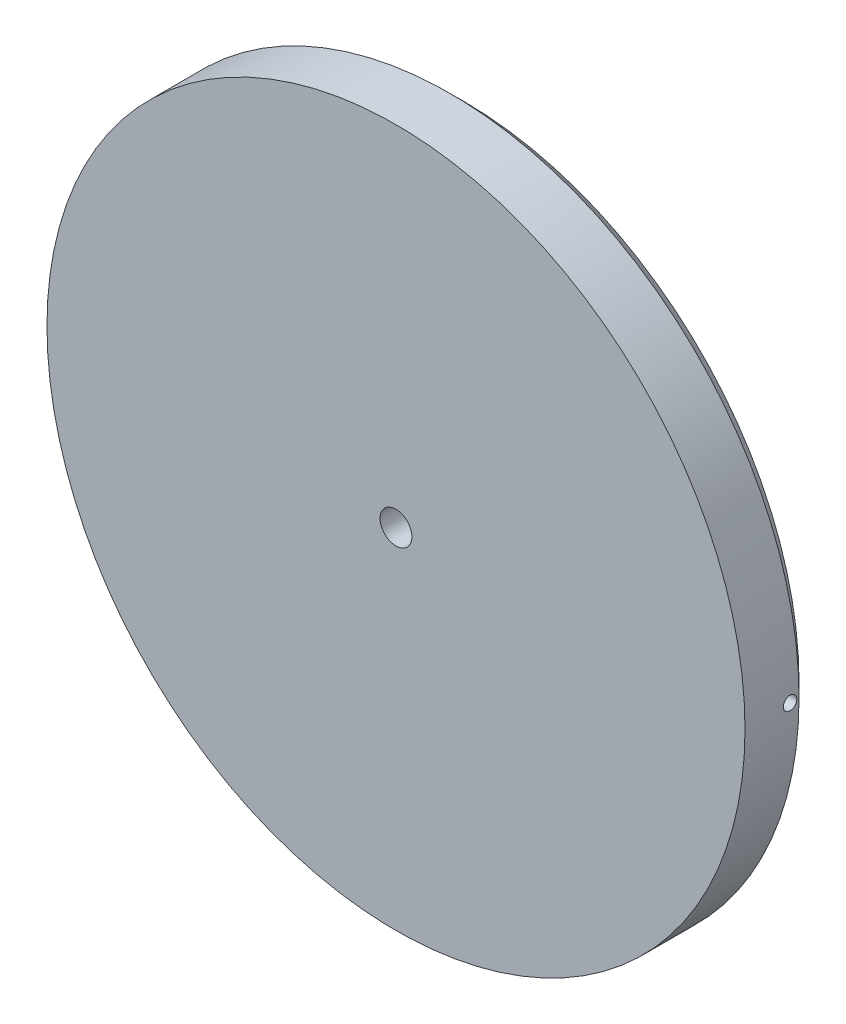
SolidWorks part; units mm, degrees
ref_plane "Front Plane" through (0, 0, 0) normal (0, 0, 1) x (1, 0, 0)
ref_plane "Top Plane" through (0, 0, 0) normal (0, 1, 0) x (1, 0, 0)
ref_plane "Right Plane" through (0, 0, 0) normal (1, 0, 0) x (0, 0, -1)
ref_axis "Z" through (0, 0, 543.0939) along (0, 0, -1)
ref_axis "X" through (17.0818, 0, 0) along (-1, 0, 0)
ref_axis "Y" through (0, 20.242, 0) along (0, -1, 0)
sketch "Sketch1" plane through (0, 0, 0) normal (0, 0, 1) x (1, 0, 0)
  circle A0 centre (0, 0) radius 77.5
  circle A1 centre (0, 0) radius 3.535
  dimension "D1" = 155
  dimension "D2" = 7.07
extrude "Boss-Extrude1" add sketch "Sketch1" against normal blind 5 and the other way blind 10
sketch "Sketch2" plane through (0, 0, 0) normal (0, 1, 0) x (1, 0, 0)
  line L0 (-16.3173, 0) -> (16.3173, 0) construction
  line L1 (0, -20.5521) -> (0, 20.5521) construction
  circle A0 centre (0, 0) radius 1.5
  dimension "D1" = 3
extrude "Cut-Extrude1" cut sketch "Sketch2" against normal through all
sketch "Sketch3" plane through (0, 0, 0) normal (1, 0, 0) x (0, 0, -1)
  circle A0 centre (0, 0) radius 1.5
  dimension "D1" = 3
extrude "Cut-Extrude2" cut sketch "Sketch3" along normal through all
chamfer "Chamfer1" distance 3 angle 45 1 edges at (77.5, 0, -5)
sketch "Sketch4" plane through (0, 0, 0) normal (0, 0, 1) x (1, 0, 0)
  circle A0 centre (0, 0) radius 3.535
  circle A2 centre (0, 0) radius 3.535 construction
  circle A3 centre (0, 0) radius 71.5
  dimension "D1" = 143
extrude "Boss-Extrude2" add sketch "Sketch4" along normal up to surface and the other way up to surface up to face at (77.5, 0, 10) other way up to face at (74.5, 0, -5)
sketch "Sketch5" plane through (0, 0, 0) normal (0, 0, 1) x (1, 0, 0)
  line L0 (0, 0) -> (0, -92.5) construction
  dimension "D1" = 92.5
equation "\"EyeDiameter\" = 155"
equation "\"BasePlaneDistance\" = \"EyeDiameter\"/2+15"
equation "\"EyeClearance\" = 2"
equation "\"EyeOD\"= \"EyeDiameter\""
equation "\"D1@Sketch1\"=\"EyeOD\""
equation "\"D2@Sketch1\"= 7.07"
equation "\"pinHoleDiameter\"= 3"
equation "\"D1@Sketch2\"=\"pinHoleDiameter\""
equation "\"D1@Sketch3\"=\"pinHoleDiameter\""
equation "\"D1@Sketch4\"=\"EyeDiameter\"-12"
equation "\"D1@Sketch5\"=\"BasePlaneDistance\""
